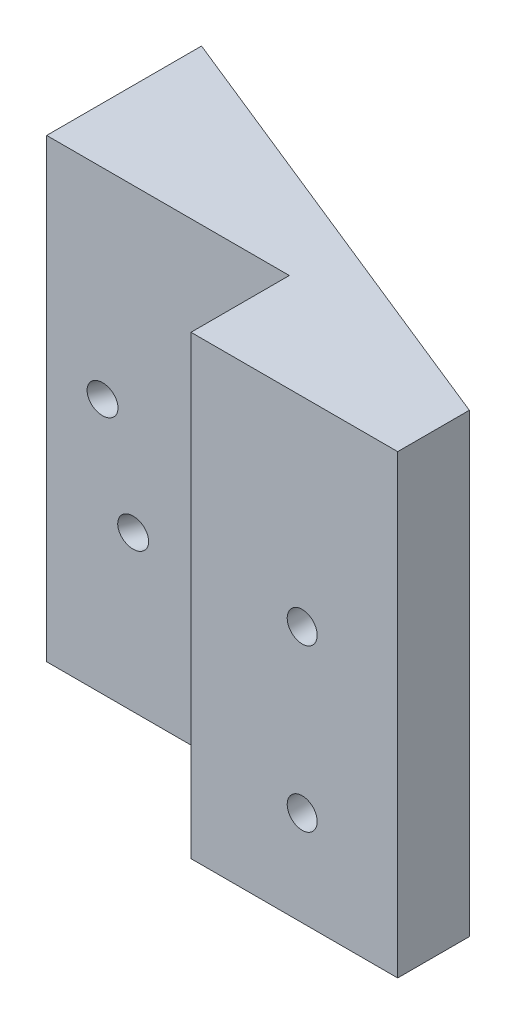
SolidWorks part; units mm, degrees
ref_plane "Front" through (0, 0, 0) normal (0, 0, 1) x (1, 0, 0)
ref_plane "Top" through (0, 0, 0) normal (0, 1, 0) x (1, 0, 0)
ref_plane "Right" through (0, 0, 0) normal (1, 0, 0) x (0, 0, -1)
sketch "Sketch1" plane through (0, 0, 0) normal (0, 1, 0) x (1, 0, 0)
  line L0 (69, 5) -> (0, 32.8778)
  line L3 (0, 5) -> (69, 5)
  line L5 (0, 32.8778) -> (0, 5)
  line L7 (0, 5) -> (69, 5)
  line L8 (0, 5) -> (0, 0)
  line L9 (0, 0) -> (69, 0)
  line L10 (69, 5) -> (69, 0)
  dimension "D1" = 5
  dimension "D2" = 22
  dimension "D3" = 69
extrude "Boss-Extrude1" add sketch "Sketch1" along normal blind 70 contours L0 L5 L3 | L9 L3 region at (23, 0, -14.2926) region at (34.5, 0, -2.5)
sketch "Sketch2" plane through (0, 70, 0) normal (0, 1, 0) x (1, 0, 0)
  line L0 (0, 32.8778) -> (0, 0) construction
  line L1 (0, 9.1) -> (37.2614, 9.1)
  line L2 (0, 9.1) -> (0, 0)
  line L3 (0, 0) -> (37.2614, 0)
  line L4 (37.2614, 9.1) -> (37.2614, 0)
  line L5 (37.2614, 9.1) -> (-18.9926, 9.1) construction
  line L6 (0, 0) -> (69, 0) construction
  line L7 (37.2614, -5.9) -> (37.2614, 4.1) construction
sketch "Sketch3" plane through (0, 70, 0) normal (0, 1, 0) x (1, 0, 0)
  line L0 (0, 32.8778) -> (0, 0) construction
  line L1 (0, 9.1) -> (37.2614, 9.1)
  line L2 (0, 9.1) -> (0, 0)
  line L3 (0, 0) -> (37.2614, 0)
  line L4 (37.2614, 9.1) -> (37.2614, 0)
  dimension "D1" = 9.1
extrude "Cut-Extrude1" cut sketch "Sketch3" against normal blind 70
sketch "Sketch4" plane through (0, 70, 0) normal (0, 1, 0) x (1, 0, 0)
  line L1 (37.2614, 0) -> (69, 0)
  line L2 (37.2614, 0) -> (37.2614, -6)
  line L3 (37.2614, -6) -> (69, -6)
  line L4 (69, 0) -> (69, -6)
  dimension "D1" = 6
extrude "Boss-Extrude2" add sketch "Sketch4" against normal blind 70
sketch "Sketch5" plane through (0, 0, 6) normal (0, 0, 1) x (1, 0, 0)
  circle A0 centre (54.3369, 39.3863) radius 2.3
  circle A1 centre (54.3369, 14.6087) radius 2.3
extrude "Cut-Extrude2" cut sketch "Sketch5" against normal blind 20
sketch "Sketch6" plane through (11.4194, 0, -28.2641) normal (0.3746, 0, -0.9272) x (-0.9272, 0, -0.3746)
  circle A0 centre (-4.5443, 39.2121) radius 2.2
  circle A1 centre (-8.9042, 23.8176) radius 2.2
  circle A2 centre (-19.9388, 43.572) radius 2.2
  circle A3 centre (-24.2988, 28.1775) radius 2
extrude "Cut-Extrude3" cut sketch "Sketch6" against normal blind 45
